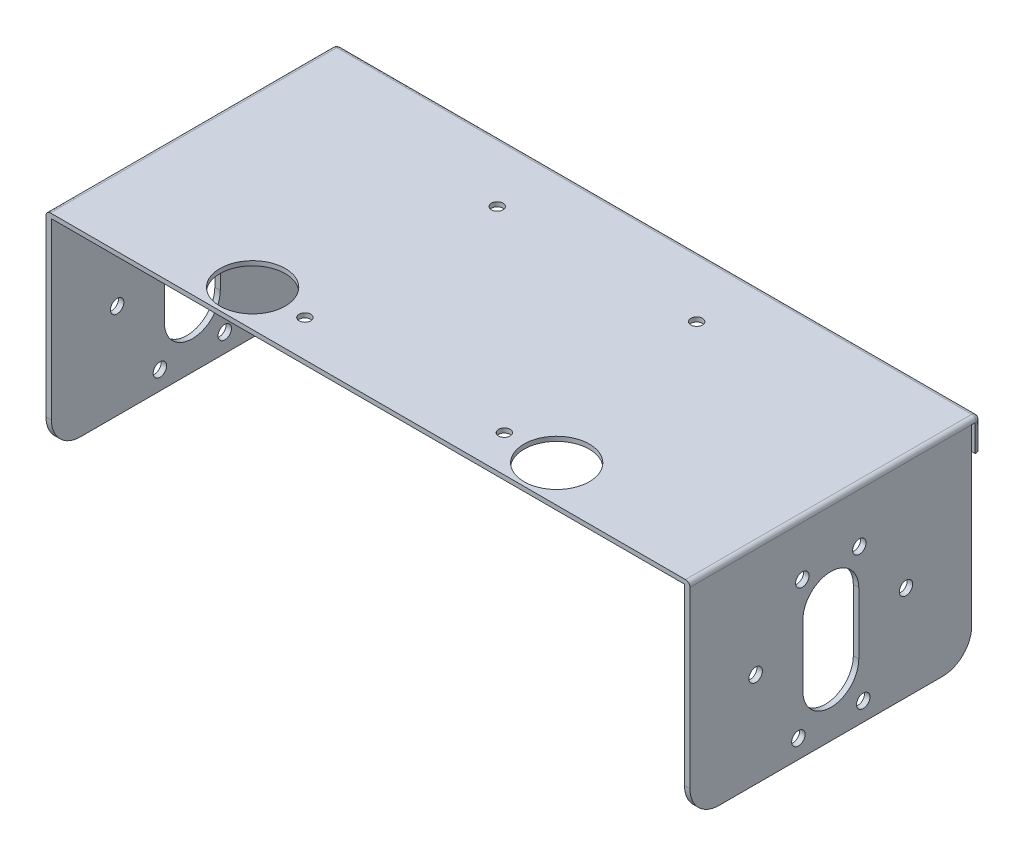
SolidWorks part; units mm, degrees
ref_plane "Plan de face" through (0, 0, 0) normal (0, 0, 1) x (1, 0, 0)
ref_plane "Plan de dessus" through (0, 0, 0) normal (0, 1, 0) x (1, 0, 0)
ref_plane "Plan de droite" through (0, 0, 0) normal (1, 0, 0) x (0, 0, -1)
sketch "Esquisse2" plane through (0, 0, 0) normal (0, 1, 0) x (1, 0, 0)
  line L0 (-72, 0) -> (72, 0)
  line L1 (-72, 0) -> (-72, 65)
  line L2 (-72, 65) -> (72, 65)
  line L3 (72, 65) -> (72, 0)
  point P3 (0, 0)
  dimension "D1" = 144
  dimension "D2" = 65
extrude "Boss.-Extru.1" add sketch "Esquisse2" along normal blind 1
sketch "Esquisse3" plane through (0, 0, 0) normal (0, -1, 0) x (1, 0, 0)
  line L0 (-72, -65) -> (-72, -63.78)
  line L1 (72, -65) -> (-72, -65) construction
  line L2 (-72, -63.78) -> (72, -63.78)
  line L3 (72, -63.78) -> (72, -65)
  line L6 (-72, -65) -> (72, -65)
  line L7 (-72, -65) -> (-72, 0) construction
  line L8 (72, 0) -> (72, -65) construction
  dimension "D1" = 1.22
extrude "Boss.-Extru.2" add sketch "Esquisse3" along normal blind 6
sketch "Esquisse6" plane through (0, 0, 0) normal (0, -1, 0) x (-1, 0, 0)
  line L0 (70.78, 0) -> (70.78, 63)
  line L1 (72, 0) -> (-72, 0) construction
  line L2 (70.78, 63) -> (72, 63)
  line L3 (72, 63.78) -> (72, 0) construction
  line L4 (72, 63) -> (72, 0)
  line L5 (72, 0) -> (70.78, 0)
  line L6 (-72, 0) -> (-72, 63)
  line L7 (-72, 0) -> (-72, 63.78) construction
  line L8 (-72, 63) -> (-70.78, 63)
  line L9 (-70.78, 63) -> (-70.78, 0)
  line L10 (-70.78, 0) -> (-72, 0)
  line L11 (72, 65) -> (-72, 65) construction
  dimension "D1" = 2
  dimension "D2" = 2
  dimension "D3" = 1.22
  dimension "D4" = 1.22
extrude "Boss.-Extru.4" add sketch "Esquisse6" along normal blind 45.5
fillet "Congé3" radius 1 1 edges at (0, 1, -65)
fillet "Congé4" radius 1 6 edges at (-72, -3, -65) (-72, 0.7071, -64.7071) (72, -3, -65) (72, 0.7071, -64.7071) (-72, 1, -32) (72, 1, -32)
sketch "Esquisse7" plane through (72, 0, 0) normal (1, 0, 0) x (0, 0, -1)
  line L0 (0, -45.5) -> (0, -39)
  line L1 (0, 0) -> (0, -45.5) construction
  line L2 (0, -45.5) -> (6.5, -45.5)
  line L3 (63, -45.5) -> (0, -45.5) construction
  line L4 (56.5, -45.5) -> (63, -45.5)
  line L5 (63, -45.5) -> (63, -39)
  line L6 (63, -45.5) -> (63, 0) construction
  arc A0 (0, -39) -> (6.5, -45.5) centre (6.5, -39) ccw
  arc A1 (63, -39) -> (56.5, -45.5) centre (56.5, -39) cw
  dimension "D1" = 6.5
  dimension "D2" = 6.5
extrude "Enlèv. mat.-Extru.2" cut sketch "Esquisse7" against normal through all
sketch "Esquisse8" plane through (0, 1, 0) normal (0, 1, 0) x (1, 0, 0)
  line L0 (-71, 64) -> (-71, 0) construction
  line L1 (71, 0) -> (71, 64) construction
  line L2 (-71, 0) -> (71, 0) construction
  circle A0 centre (-34, 8.2) radius 7.3
  circle A1 centre (34, 8.2) radius 7.3
  dimension "D3" = 14.6
  dimension "D4" = 8.2
  dimension "D1" = 37
  dimension "D2" = 37
extrude "Enlèv. mat.-Extru.3" cut sketch "Esquisse8" against normal through all
sketch "Esquisse9" plane through (0, 1, 0) normal (0, 1, 0) x (1, 0, 0)
  line L1 (-71, 0) -> (71, 0) construction
  circle A0 centre (-22.3, 8.2) radius 1.3
  circle A1 centre (22.3, 8.2) radius 1.3
  circle A2 centre (-34, 8.2) radius 7.3 construction
  circle A3 centre (34, 8.2) radius 7.3 construction
  circle A4 centre (-22.3, 51.2) radius 1.3
  circle A5 centre (22.3, 51.2) radius 1.3
  dimension "D3" = 8.2
  dimension "D1" = 11.7
  dimension "D2" = 11.7
  dimension "D4" = 43
extrude "Enlèv. mat.-Extru.4" cut sketch "Esquisse9" against normal through all
sketch "Esquisse10" plane through (72, 0, 0) normal (1, 0, 0) x (0, 0, -1)
  line L0 (31.5, -32.75) -> (31.5, -18.95) construction
  line L1 (25.25, -32.75) -> (25.25, -18.95)
  line L2 (37.75, -32.75) -> (37.75, -18.95)
  line L4 (56.5, -45.5) -> (6.5, -45.5) construction
  line L5 (0, 1) -> (64, 1) construction
  arc A0 (25.25, -32.75) -> (37.75, -32.75) centre (31.5, -32.75) ccw
  arc A1 (37.75, -18.95) -> (25.25, -18.95) centre (31.5, -18.95) ccw
  point P2 (31.5, -25.85)
  point P9 (31.5, -45.5)
  point P10 (31.5, -12.7)
  point P11 (31.5, -39)
  dimension "D4" = 13.7
  dimension "D1" = 12.5
  dimension "D2" = 12.5
  dimension "D3" = 26.3
extrude "Enlèv. mat.-Extru.6" cut sketch "Esquisse10" against normal through all
ref_plane "Plan1" through (0, 0, -31.5) normal (0, 0, -1) x (-1, 0, 0)
sketch "Esquisse11" plane through (72, 0, 0) normal (1, 0, 0) x (0, 0, -1)
  line L0 (37.75, -32.75) -> (37.75, -18.95) construction
  circle A0 centre (38.7533, -41.35) radius 1.5
  circle A1 centre (14.6906, -24.2844) radius 1.5
  circle A2 centre (37.8762, -11.05) radius 1.5
  arc A3 (25.25, -32.75) -> (37.75, -32.75) centre (31.5, -32.75) ccw construction
  point P10 (39.514, -39.4511)
  dimension "D1" = 3
  dimension "D3" = 3
  dimension "D5" = 3
  dimension "D7" = 8.6
  dimension "D8" = 23.1856
  dimension "D2" = 1.0033
  dimension "D4" = 24.0627
  dimension "D6" = 30.3
  dimension "D9" = 17.0656
extrude "Enlèv. mat.-Extru.7" cut sketch "Esquisse11" against normal through all
mirror "Symétrie1" about plane through (0, 0, -31.5) normal (0, 0, -1) of "Enlèv. mat.-Extru.7"
